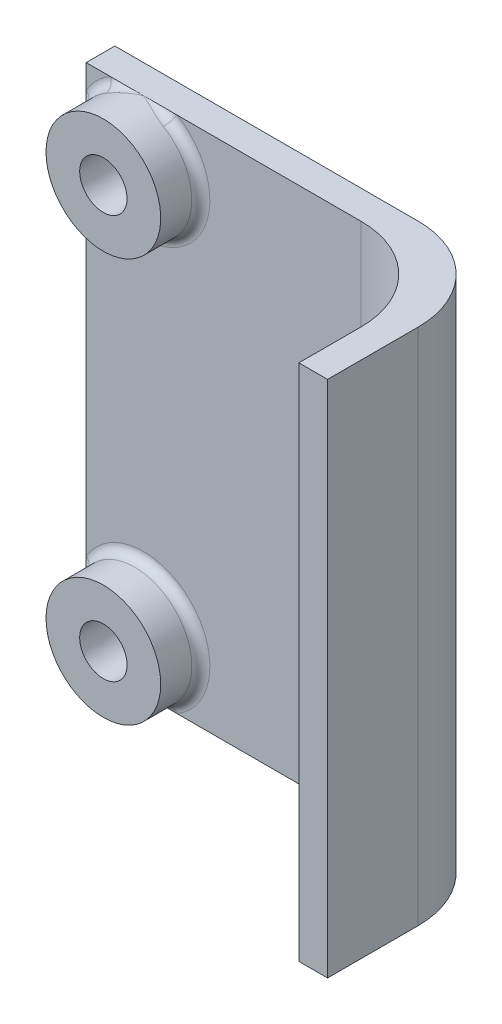
SolidWorks part; units mm, degrees
material "ABS"
ref_plane "X-Y Datum" through (0, 0, 0) normal (0, 0, 1) x (1, 0, 0)
ref_plane "X-Z Datum" through (0, 0, 0) normal (0, 1, 0) x (1, 0, 0)
ref_plane "Y-Z Datum" through (0, 0, 0) normal (1, 0, 0) x (0, 0, -1)
sketch "Sketch1" plane through (0, 0, 0) normal (0, 1, 0) x (1, 0, 0)
  line L0 (0, 0) -> (0, 20.193)
  line L1 (0, -43.0151) -> (0, 43.0151) construction
  line L4 (0, 0) -> (-3.175, 0)
  line L5 (-55, 0) -> (55, 0) construction
  line L10 (0, 20.193) -> (-38.1589, 20.193)
  line L13 (-38.1589, 20.193) -> (-38.1589, 17.018) construction
  line L14 (-38.1589, 17.018) -> (-3.175, 17.018)
  line L15 (-3.175, 17.018) -> (-3.175, 0)
  line L16 (-38.1589, 20.193) -> (-43.7469, 20.193)
  line L17 (-43.7469, 20.193) -> (-43.7469, 17.018)
  line L18 (-43.7469, 17.018) -> (-38.1589, 17.018)
  dimension "D1" = 20.193
  dimension "D3" = 3.175
extrude "Boss-Extrude1" add sketch "Sketch1" along normal blind 57.404
fillet "Fillet1" radius 10.16 2 edges at (0, 28.702, -20.193) (-3.175, 28.702, -17.018)
sketch "Sketch2" plane through (0, 0, -20.193) normal (0, 0, -1) x (-1, 0, 0)
  line L0 (43.7469, 57.404) -> (37.3969, 57.404) construction
  line L1 (10.16, 57.404) -> (43.7469, 57.404) construction
  line L2 (37.3969, 57.404) -> (37.3969, 51.054) construction
  line L3 (43.7469, 28.702) -> (-4.7468, 28.702) construction
  line L4 (43.7469, 57.404) -> (43.7469, 0) construction
  circle A0 centre (37.3969, 51.054) radius 6.35
  circle A1 centre (37.3969, 51.054) radius 2.625
  circle A2 centre (37.3969, 6.35) radius 2.625
  circle A3 centre (37.3969, 6.35) radius 6.35
extrude "Boss-Extrude2" add sketch "Sketch2" against normal blind 7.62
sketch "Sketch3" plane through (0, 0, -17.018) normal (0, 0, 1) x (1, 0, 0)
  circle A0 centre (-37.3969, 51.054) radius 2.625
  circle A1 centre (-37.3969, 6.35) radius 2.625
extrude "Cut-Extrude1" cut sketch "Sketch3" against normal through all
fillet "Fillet2" radius 1 4 edges at (-41.8871, 55.5441, -17.018) (-32.9068, 46.5639, -17.018) (-32.9068, 10.8401, -17.018) (-41.8871, 1.8599, -17.018)
